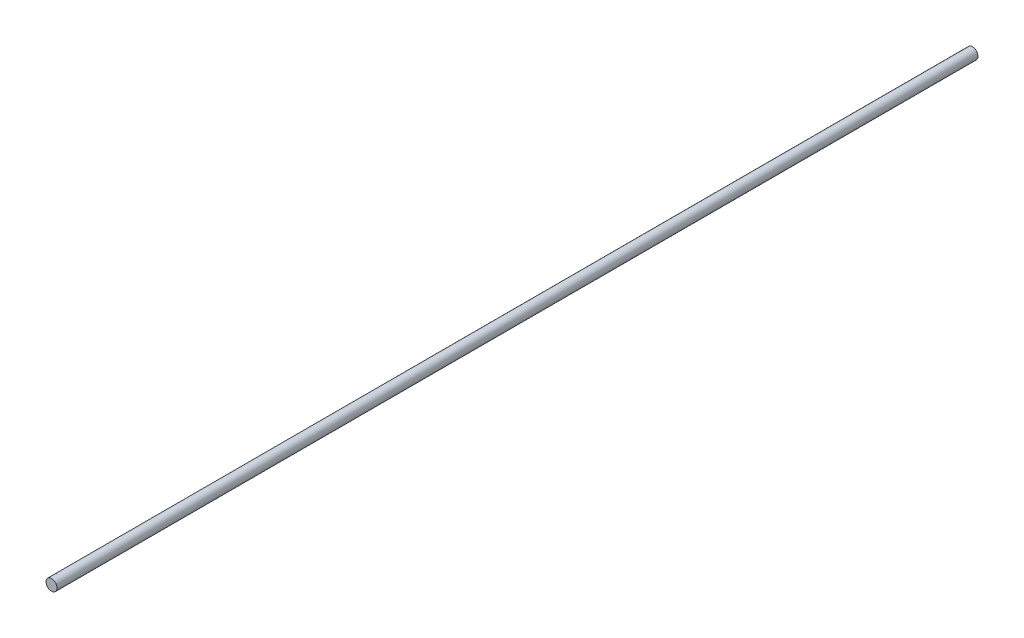
SolidWorks part; units mm, degrees
ref_plane "Спереди" through (0, 0, 0) normal (0, 0, 1) x (1, 0, 0)
ref_plane "Сверху" through (0, 0, 0) normal (0, 1, 0) x (1, 0, 0)
ref_plane "Справа" through (0, 0, 0) normal (1, 0, 0) x (0, 0, -1)
sketch "Эскиз1" plane through (0, 0, 0) normal (0, 0, 1) x (-1, 0, 0)
  circle A0 centre (-6.5, 15.25) radius 2.9995
extrude "Бобышка-Вытянуть1" add sketch "Эскиз1" along normal blind 500 contours A0
